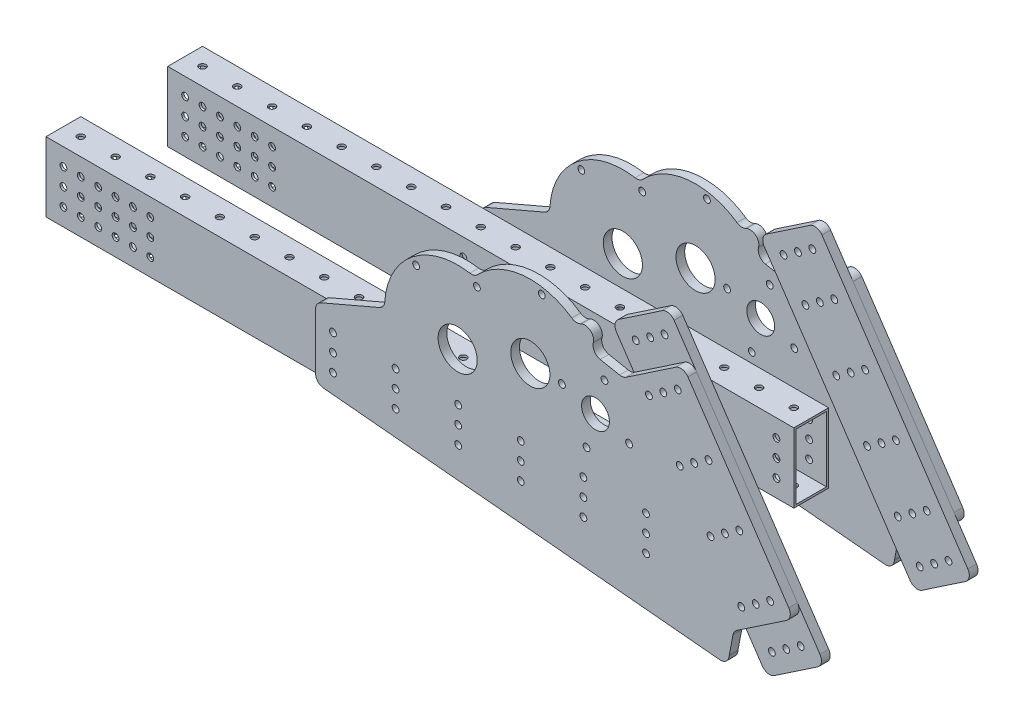
SolidWorks part; units mm, degrees
other "Markup1"
sketch "Sketch2"
sketch "Sketch9" plane through (0, 0, 0) normal (0, 0, 1) x (1, 0, 0)
sketch "Sketch12" plane through (116.0373, 167.646, 63.5) normal (0, 0, 1) x (1, 0, 0)
material "6061-T6 (SS)"
ref_plane "Front Plane" through (0, 0, 0) normal (0, 0, 1) x (1, 0, 0)
ref_plane "Top Plane" through (0, 0, 0) normal (0, 1, 0) x (1, 0, 0)
ref_plane "Right Plane" through (0, 0, 0) normal (1, 0, 0) x (0, 0, -1)
sketch "Grid" plane through (0, 0, 0) normal (0, 0, 1) x (1, 0, 0)
  line L0 (-23.2766, 0) -> (153.3593, 0) construction
  line L1 (0, 0) -> (0, 151.4205) construction
  line L6 (-1009.65, 1168.4) -> (-1009.65, 0) construction
  line L15 (-361.95, 520.7) -> (-803.275, 520.7)
  line L16 (-361.95, 520.7) -> (-361.95, 0)
  line L17 (-361.95, 0) -> (-803.275, 0)
  line L18 (-803.275, 520.7) -> (-803.275, 0)
  line L19 (-803.275, 0) -> (-1244.6, 0)
  line L20 (-803.275, 0) -> (-803.275, 825.5)
  line L21 (-803.275, 825.5) -> (-1244.6, 825.5)
  line L22 (-1244.6, 0) -> (-1244.6, 825.5)
  line L23 (-1030.732, 0) -> (-988.568, 0)
  line L24 (-1030.732, 0) -> (-1030.732, 1168.4)
  line L25 (-1030.732, 1168.4) -> (-988.568, 1168.4)
  line L26 (-988.568, 0) -> (-988.568, 1168.4)
  line L27 (-598.932, 0) -> (-556.768, 0)
  line L28 (-598.932, 0) -> (-598.932, 863.6)
  line L29 (-598.932, 863.6) -> (-556.768, 863.6)
  line L30 (-556.768, 0) -> (-556.768, 863.6)
  line L31 (-577.85, 863.6) -> (-577.85, 0) construction
  line L32 (-361.95, 520.7) -> (-361.95, 596.9) construction
  line L33 (-803.275, 825.5) -> (-803.275, 901.7) construction
  line L34 (-370.0766, 0) -> (-263.7141, 304.8)
  line L35 (-263.7141, 304.8) -> (-157.3516, 0)
  line L36 (-157.3516, 0) -> (-370.0766, 0)
  circle A0 centre (-100.3958, 159.9664) radius 120.65
  dimension "D3" = 241.3
  dimension "D2" = 76.2
  dimension "D4" = 304.8
  dimension "D5" = 212.725
  dimension "D7" = 42.164
  dimension "D8" = 520.7
  dimension "D9" = 304.8
  dimension "D10" = 1168.4
  dimension "D11" = 863.6
  dimension "D12" = 361.95
  dimension "D13" = 577.85
  dimension "D14" = 803.275
  dimension "D15" = 1009.65
sketch "ChassisXY" plane through (0, 0, 0) normal (0, 0, 1) x (1, 0, 0)
  line L0 (755.65, 93.726) -> (95.25, 93.726)
  line L1 (755.65, 93.726) -> (755.65, 42.926)
  line L2 (755.65, 42.926) -> (95.25, 42.926)
  line L3 (95.25, 93.726) -> (95.25, 42.926)
  line L15 (736.7108, 119.126) -> (675.4349, 119.126)
  line L16 (787.4, 42.926) -> (768.35, 42.926)
  line L19 (63.5, 169.926) -> (82.55, 169.926)
  line L20 (736.7108, 119.126) -> (694.5957, 90.719) construction
  line L21 (736.7108, 119.126) -> (717.55, 147.533) construction
  line L22 (694.5957, 90.719) -> (675.4349, 119.126) construction
  line L23 (717.55, 147.533) -> (675.4349, 119.126) construction
  line L27 (63.5, 169.926) -> (63.5, 42.926)
  line L31 (88.9, 42.926) -> (88.9, 1979.9925) construction
  line L32 (62.806, 1979.9925) -> (762, 1979.9925) construction
  line L33 (63.5, 42.926) -> (82.55, 42.926)
  line L36 (88.9, 1320.8) -> (762, 1320.8) construction
  line L37 (88.9, 988.6997) -> (131.0151, 1017.1067) construction
  line L45 (63.5, 42.926) -> (31.75, 42.926)
  line L46 (717.55, 147.533) -> (675.4349, 119.126) construction
  line L47 (717.55, 147.533) -> (-518.4596, 1979.9925) construction
  line L48 (675.4349, 119.126) -> (-560.5747, 1951.5855) construction
  line L49 (-518.4596, 1979.9925) -> (-560.5747, 1951.5855) construction
  line L50 (63.5, 42.926) -> (63.5, 169.926)
  line L51 (0, 74.676) -> (0, 138.176)
  line L52 (31.75, 169.926) -> (63.5, 169.926)
  line L54 (425.45, 93.726) -> (425.45, 42.926) construction
  line L55 (762, 42.926) -> (762, 1979.9925) construction
  line L56 (819.15, 169.926) -> (787.4, 169.926)
  line L57 (850.9, 74.676) -> (850.9, 138.176)
  line L58 (787.4, 42.926) -> (787.4, 169.926)
  line L59 (787.4, 42.926) -> (819.15, 42.926)
  line L60 (82.55, 169.926) -> (82.55, 42.926)
  line L61 (768.35, 169.926) -> (768.35, 42.926)
  line L62 (787.4, 169.926) -> (768.35, 169.926)
  line L63 (787.4, 169.926) -> (787.4, 42.926)
  line L64 (0, 0) -> (0, 200151.4205) construction
  line L65 (-200023.2766, 0) -> (200153.3593, 0) construction
  line L66 (95.25, 152.4) -> (755.65, 152.4) construction
  arc A5 (31.75, 169.926) -> (0, 138.176) centre (31.75, 138.176) ccw
  arc A6 (0, 74.676) -> (31.75, 42.926) centre (31.75, 74.676) ccw
  circle A7 centre (31.75, 74.676) radius 31.75 construction
  circle A8 centre (31.75, 138.176) radius 31.75 construction
  circle A9 centre (819.15, 138.176) radius 31.75 construction
  circle A10 centre (819.15, 74.676) radius 31.75 construction
  arc A11 (850.9, 74.676) -> (819.15, 42.926) centre (819.15, 74.676) cw
  arc A12 (819.15, 169.926) -> (850.9, 138.176) centre (819.15, 138.176) cw
  dimension "D3" = 63.5
  dimension "D1" = 50.8
  dimension "D2" = 56
  dimension "D4" = 38.1
  dimension "D5" = 50.8
  dimension "D6" = 12.7
  dimension "D7" = 19.05
  dimension "D8" = 42.926
  dimension "D9" = 109.474
  dimension "D10" = 25.4
  dimension "D12" = 660.4
  dimension "D13" = 6.35
ref_plane "Plane1" through (561.5696, 378.7835, 0) normal (0.829, 0.5592, 0) x (-0.5592, 0.829, 0)
sketch "carriage geo" plane through (0, 0, 0) normal (0, 0, 1) x (1, 0, 0)
  line L1 (116.0373, 195.326) -> (624.0373, 195.326)
  line L2 (116.0373, 195.326) -> (116.0373, 246.126)
  line L3 (116.0373, 246.126) -> (624.0373, 246.126)
  line L4 (624.0373, 195.326) -> (624.0373, 246.126)
  line L6 (624.0373, 195.326) -> (700.6322, 195.326) construction
  line L17 (717.55, 147.533) -> (-518.4596, 1979.9925) construction
  line L24 (624.0373, 246.126) -> (666.3671, 246.126) construction
  line L33 (666.3671, 246.126) -> (700.6322, 195.326) construction
  line L35 (675.4349, 119.126) -> (-560.5747, 1951.5855) construction
  line L64 (755.65, 93.726) -> (95.25, 93.726) construction
  circle A0 centre (154.1373, 220.726) radius 14.2875
  circle A58 centre (256.8816, 507.741) radius 25.4
  line B0 (120.4355, 364.2548) -> (144.4436, 355.656) construction
  line B1 (345.3934, 565.2279) -> (248.3868, 535.0242)
  line B2 (339.9907, 375.4447) -> (343.9447, 374.0285) construction
  line B3 (348.2442, 386.0326) -> (300.3235, 403.196) construction
  line B4 (308.577, 413.7839) -> (348.5895, 399.4529)
  line B5 (107.1432, 327.1426) -> (206.8255, 291.4401)
  line B6 (112.3162, 360.4178) -> (103.3062, 335.2619)
  line B7 (352.5436, 398.0367) -> (348.5895, 399.4529) construction
  line B8 (366.599, 439.1494) -> (341.413, 442.4393) construction
  line B9 (353.8882, 537.9448) -> (341.413, 442.4393) construction
  line B10 (343.9447, 374.0285) -> (352.5436, 398.0367)
  line B11 (348.5895, 399.4529) -> (308.577, 413.7839)
  line B12 (304.6229, 415.2001) -> (296.0241, 391.1919)
  line B13 (299.9781, 389.7757) -> (339.9907, 375.4447)
  line B14 (140.4752, 344.576) -> (141.8914, 348.5301) construction
  line B15 (129.3385, 325.9381) -> (133.2925, 324.5219) construction
  line B16 (110.7006, 337.0748) -> (109.2844, 333.1207) construction
  line B17 (121.8372, 355.7127) -> (117.8832, 357.1289) construction
  line B18 (117.8832, 357.1289) -> (110.7006, 337.0748)
  line B19 (109.2844, 333.1207) -> (129.3385, 325.9381)
  line B20 (141.8914, 348.5301) -> (121.8372, 355.7127)
  line B21 (133.2925, 324.5219) -> (140.4752, 344.576)
  line B22 (296.0241, 391.1919) -> (299.9781, 389.7757) construction
  line B23 (308.577, 413.7839) -> (304.6229, 415.2001) construction
  arc B24 (248.3868, 535.0242) -> (233.4586, 491.3735) centre (256.8816, 507.741) ccw
  circle B25 centre (256.8816, 507.741) radius 3.1877
  circle B26 centre (353.8882, 537.9448) radius 3.1877
  arc B27 (107.1432, 327.1426) -> (103.3062, 335.2619) centre (109.2844, 333.1207) cw
  circle B28 centre (341.413, 442.4393) radius 30 construction
  arc B29 (121.2422, 363.9009) -> (112.3162, 360.4178) centre (118.2943, 358.2767) ccw
  arc B30 (233.4586, 491.3735) -> (121.2422, 363.9009) centre (161.817, 441.3116) cw
  circle B31 centre (341.413, 442.4393) radius 25.4 construction
  circle B32 centre (366.599, 439.1494) radius 2.4892
  circle B33 centre (338.1231, 417.2533) radius 2.4892
  circle B34 centre (316.2269, 445.7292) radius 2.4892
  circle B35 centre (344.7029, 467.6254) radius 2.4892
  circle B36 centre (341.413, 442.4393) radius 10.16
  circle B37 centre (147.3899, 326.2177) radius 2.4892
  arc B38 (376.4624, 520.4251) -> (367.6342, 457.9958) centre (426.6271, 481.4924) ccw
  arc B39 (367.6342, 457.9958) -> (206.8255, 291.4401) centre (249.6484, 411.0026) cw
  arc B40 (133.2925, 324.5219) -> (129.3385, 325.9381) centre (131.3155, 325.23) cw
  arc B41 (343.9447, 374.0285) -> (339.9907, 375.4447) centre (341.9677, 374.7366) cw
  arc B42 (296.0241, 391.1919) -> (299.9781, 389.7757) centre (298.0011, 390.4838) ccw
  arc B43 (352.5436, 398.0367) -> (348.5895, 399.4529) centre (350.5666, 398.7448) ccw
  arc B44 (304.6229, 415.2001) -> (308.577, 413.7839) centre (306.5999, 414.492) cw
  arc B45 (109.2844, 333.1207) -> (110.7006, 337.0748) centre (109.9925, 335.0977) cw
  arc B46 (117.8832, 357.1289) -> (121.8372, 355.7127) centre (119.8602, 356.4208) cw
  arc B47 (141.8914, 348.5301) -> (140.4752, 344.576) centre (141.1833, 346.553) cw
  circle B48 centre (353.8882, 537.9448) radius 28.575
  line B49 (343.9447, 374.0285) -> (296.1197, 391.1577)
  line B50 (343.9447, 374.0285) -> (318.251, 302.291)
  line B51 (296.1197, 391.1577) -> (270.426, 319.4201)
  line B52 (318.251, 302.291) -> (270.426, 319.4201) construction
  line B53 (141.8571, 348.4344) -> (133.2925, 324.5219) construction
  line B54 (165.7696, 339.8698) -> (237.5071, 314.1761)
  line B55 (157.205, 315.9573) -> (228.9426, 290.2636)
  line B56 (237.5071, 314.1761) -> (228.9426, 290.2636) construction
  line B57 (161.4873, 327.9136) -> (233.2249, 302.2198) construction
  line B58 (165.7696, 339.8698) -> (157.205, 315.9573)
  line B59 (133.2925, 324.5219) -> (157.205, 315.9573) construction
  line B60 (141.8571, 348.4344) -> (165.7696, 339.8698) construction
  line B61 (308.4359, 312.5514) -> (331.9885, 378.3108) construction
  line B62 (320.0322, 382.5931) -> (294.3385, 310.8556) construction
  arc B63 (155.075, 274.6929) -> (165.7608, 168.0174) centre (154.1373, 220.726) ccw
  circle B64 centre (176.5553, 212.6967) radius 2.4892
  circle B65 centre (158.3928, 197.2968) radius 2.4892
  circle B66 centre (135.9748, 205.3261) radius 2.4892
  circle B67 centre (131.7194, 228.7553) radius 2.4892
  circle B68 centre (149.8819, 244.1552) radius 2.4892
  circle B69 centre (172.2999, 236.1259) radius 2.4892
  circle B70 centre (154.1373, 220.726) radius 23.8125 construction
  circle B71 centre (308.4359, 312.5514) radius 2.4892
  arc B72 (165.7608, 168.0174) -> (155.075, 274.6929) centre (154.1373, 220.726) ccw construction
  circle B73 centre (227.2467, 304.361) radius 2.4892
  circle B74 centre (284.5234, 321.116) radius 2.4892
  arc B75 (290.7123, 376.06) -> (193.2811, 330.0162) centre (218.9748, 401.7538) cw
  arc B76 (318.251, 302.291) -> (165.7608, 168.0174) centre (120.5341, 373.1059) cw
  circle B77 centre (312.7182, 324.5077) radius 2.4892
  circle B78 centre (288.8057, 333.0722) radius 2.4892
  circle B79 centre (317.0005, 336.4639) radius 2.4892
  circle B80 centre (293.088, 345.0285) radius 2.4892
  circle B81 centre (321.2828, 348.4202) radius 2.4892
  circle B82 centre (297.3703, 356.9847) radius 2.4892
  circle B83 centre (325.5651, 360.3764) radius 2.4892
  circle B84 centre (301.6526, 368.941) radius 2.4892
  circle B85 centre (329.8473, 372.3327) radius 2.4892
  circle B86 centre (305.9348, 380.8972) radius 2.4892
  arc B87 (162.2796, 314.1398) -> (155.075, 274.6929) centre (155.4279, 295.0098) cw
  circle B88 centre (215.2905, 308.6433) radius 2.4892
  circle B89 centre (203.3342, 312.9256) radius 2.4892
  circle B90 centre (191.378, 317.2079) radius 2.4892
  circle B91 centre (179.4217, 321.4901) radius 2.4892
  circle B92 centre (167.4655, 325.7724) radius 2.4892
  dimension "D2" = 28.575
  dimension "D3" = 25.4
  dimension "D4" = 38.1
  dimension "D8" = 101.6
  dimension "D5" = 50.8
  dimension "D1" = 50.8
  dimension "D6" = 12.7
  dimension "D7" = 508
sketch_block_instance "Block25-1"
sketch_block "Block25"
sketch_block_instance "Block26-1"
sketch_block "Block26"
sketch "carrriageyz" plane through (561.5696, 378.7835, 0) normal (0.829, 0.5592, 0) x (-0.5592, 0.829, 0)
  line L0 (-313.2035, 69.85) -> (769.957, 69.85) construction
  line L1 (769.957, -69.85) -> (-313.2035, -69.85) construction
  line L2 (-262.4035, 69.85) -> (-262.4035, -69.85) construction
  line L4 (-313.2035, 69.85) -> (-313.2035, -69.85) construction
  line L5 (-313.2035, 0) -> (-278.9385, 0) construction
  line L6 (769.957, 69.85) -> (769.957, -69.85) construction
  line L7 (-249.7114, 57.15) -> (-249.7114, 50.8)
  line L8 (-249.7114, 57.15) -> (-97.3114, 57.15)
  line L9 (-249.7114, 50.8) -> (-97.3114, 50.8)
  line L10 (-97.3114, 57.15) -> (-97.3114, 50.8)
  line L11 (1088.9959, 0) -> (-1088.9959, 0) construction
  line L12 (-97.3114, -57.15) -> (-97.3114, -50.8)
  line L13 (-249.7114, -50.8) -> (-97.3114, -50.8)
  line L14 (-249.7114, -57.15) -> (-97.3114, -57.15)
  line L15 (-249.7114, -57.15) -> (-249.7114, -50.8)
  line L16 (-218.5469, 31.75) -> (-148.6639, 31.75)
  line L17 (-174.4547, 57.15) -> (-206.8488, 57.15)
  line L19 (-221.2897, -57.15) -> (-160.0138, -57.15)
  line L21 (-219.5489, -57.15) -> (-127.4739, -57.15)
  line L22 (-219.5489, 63.5) -> (-127.4739, 63.5)
  line L23 (-219.5489, 63.5) -> (-219.5489, 57.15)
  line L24 (-219.5489, 57.15) -> (-127.4739, 57.15)
  line L25 (-127.4739, 63.5) -> (-127.4739, 57.15)
  line L26 (-127.4739, -63.5) -> (-127.4739, -57.15)
  line L27 (-219.5489, -63.5) -> (-127.4739, -63.5)
  line L28 (-219.5489, -63.5) -> (-219.5489, -57.15)
  line L29 (-218.5469, 31.75) -> (-218.5469, -31.75)
  line L30 (-218.5469, -31.75) -> (-148.6639, -31.75)
  line L31 (-148.6639, 31.75) -> (-148.6639, -31.75)
  line L33 (-97.3114, -69.1134) -> (-125.8864, -69.1134)
  line L34 (-97.3114, 57.15) -> (-125.8864, 57.15)
  line L35 (-97.3114, 57.15) -> (-97.3114, 69.1134)
  line L36 (-97.3114, 69.1134) -> (-125.8864, 69.1134)
  line L37 (-125.8864, 57.15) -> (-125.8864, 69.1134)
  line L38 (-249.7114, 57.15) -> (-221.1364, 57.15)
  line L39 (-249.7114, 57.15) -> (-249.7114, 69.1134)
  line L40 (-249.7114, 69.1134) -> (-221.1364, 69.1134)
  line L41 (-221.1364, 57.15) -> (-221.1364, 69.1134)
  line L42 (-125.8864, -57.15) -> (-125.8864, -69.1134)
  line L43 (-97.3114, -57.15) -> (-125.8864, -57.15)
  line L44 (-97.3114, -57.15) -> (-97.3114, -69.1134)
  line L45 (-249.7114, -69.1134) -> (-221.1364, -69.1134)
  line L46 (-221.1364, -57.15) -> (-221.1364, -69.1134)
  line L47 (-249.7114, -57.15) -> (-221.1364, -57.15)
  line L48 (-249.7114, -57.15) -> (-249.7114, -69.1134)
  line L49 (-111.5989, 69.1134) -> (-111.5989, -69.1134) construction
  line L50 (-235.4239, 69.1134) -> (-235.4239, -69.1134) construction
  point P4 (-313.2035, 0)
  point P31 (-148.6639, 0)
  point P41 (-190.6518, 57.15)
  point P53 (-111.5989, 0)
  dimension "D1" = 139.7
  dimension "D2" = 12.7
  dimension "D3" = 6.35
  dimension "D4" = 63.5
  dimension "D5" = 6.35
  dimension "D6" = 152.4
  dimension "D7" = 28.575
  dimension "D8" = 11.9634
  dimension "D9" = 50.8
  dimension "D10" = 1.5875
  dimension "D11" = 1.5875
ref_plane "bearing block interface plane" through (0, 0, 57.15) normal (0, 0, 1) x (1, 0, 0)
sketch "bearing block interface plate" plane through (0, 0, 57.15) normal (0, 0, 1) x (1, 0, 0)
  line L0 (529.0514, 336.1484) -> (571.1665, 364.5554)
  line L1 (529.0514, 336.1484) -> (642.6794, 167.688)
  line L2 (571.1665, 364.5554) -> (684.7945, 196.095)
  line L3 (642.6794, 167.688) -> (684.7945, 196.095)
  line L4 (675.4349, 119.126) -> (-560.5747, 1951.5855) construction
  line L5 (717.55, 147.533) -> (-518.4596, 1979.9925) construction
  line L6 (635.5777, 178.2167) -> (677.6928, 206.6237) construction
  line L7 (585.8654, 251.9182) -> (627.9805, 280.3252) construction
  line L8 (626.7005, 191.3777) -> (668.8156, 219.7847) construction
  line L10 (545.0304, 312.4586) -> (587.1455, 340.8656) construction
  line L12 (528.3092, 320.3288) -> (546.682, 332.7214) construction
  line L15 (606.2073, 289.894) -> (628.6962, 256.5529) construction
  line L16 (522.4272, 322.7212) -> (526.7202, 333.2764) construction
  line L17 (529.0514, 336.1484) -> (536.1532, 325.6196) construction
  line L18 (527.0768, 314.0996) -> (540.247, 311.4938) construction
  line L19 (627.7485, 166.576) -> (639.1433, 166.6024) construction
  line L20 (621.4964, 174.1167) -> (624.014, 187.3041) construction
  circle A0 centre (646.1065, 185.3185) radius 2.4892
  circle A1 centre (656.6352, 192.4202) radius 2.4892
  circle A2 centre (667.164, 199.522) radius 2.4892
  circle A3 centre (567.7395, 346.9249) radius 2.4892
  circle A4 centre (557.2107, 339.8231) radius 2.4892
  circle A5 centre (546.682, 332.7214) radius 2.4892
  arc A7 (522.4272, 322.7212) -> (527.0768, 314.0996) centre (528.3092, 320.3288) ccw construction
  circle A12 centre (562.6609, 309.0316) radius 2.4892
  circle A13 centre (573.1897, 316.1334) radius 2.4892
  circle A14 centre (583.7185, 323.2351) radius 2.4892
  circle A15 centre (606.2073, 289.894) radius 2.4892
  circle A16 centre (595.6786, 282.7922) radius 2.4892
  circle A17 centre (585.1498, 275.6905) radius 2.4892
  circle A18 centre (628.6962, 256.5529) radius 2.4892
  circle A19 centre (618.1674, 249.4511) radius 2.4892
  circle A20 centre (607.6387, 242.3494) radius 2.4892
  circle A21 centre (651.1851, 223.2117) radius 2.4892
  circle A22 centre (640.6563, 216.11) radius 2.4892
  circle A23 centre (630.1275, 209.0082) radius 2.4892
  arc A24 (526.7202, 333.2764) -> (529.0514, 336.1484) centre (532.6023, 330.884) cw construction
  arc A25 (540.247, 311.4938) -> (545.0304, 312.4586) centre (541.4795, 317.723) ccw construction
  arc A26 (639.1433, 166.6024) -> (642.6794, 167.688) centre (639.1286, 172.9523) ccw construction
  arc A27 (627.7485, 166.576) -> (621.4964, 174.1167) centre (627.7337, 172.9259) cw construction
  arc A28 (624.014, 187.3041) -> (626.7005, 191.3777) centre (630.2514, 186.1133) cw construction
  point P28 (617.4518, 273.2234)
  dimension "D3" = 4.9784
  dimension "D8" = 12.7
  dimension "D10" = 2
  dimension "D13" = 6.35
  dimension "D1" = 12.7
  dimension "D2" = 12.7
  dimension "D4" = 12.7
  dimension "D5" = 28.575
  dimension "D6" = 203.2
  dimension "D7" = 4.7625
  dimension "D9" = 9.4615
  dimension "D11" = 4
  dimension "D12" = 12.7
extrude "Boss-Extrude1" add sketch "bearing block interface plate" against normal blind 6.35
fillet "Fillet2" radius 6.35 4 edges at (642.6794, 167.688, 53.975) (571.1665, 364.5554, 53.975) (529.0514, 336.1484, 53.975) (684.7945, 196.095, 53.975)
ref_plane "carriage support plane" through (0, 0, 63.5) normal (0, 0, 1) x (1, 0, 0)
sketch "plate+gb" plane through (0, 0, 63.5) normal (0, 0, 1) x (1, 0, 0)
  line L1 (717.55, 147.533) -> (-518.4596, 1979.9925) construction
  line L3 (116.0373, 195.326) -> (624.0373, 195.326) construction
  line L4 (319.2373, 195.326) -> (627.1295, 166.4772)
  line L7 (668.3717, 220.4428) -> (587.5893, 340.2076)
  line L8 (509.1308, 327.7242) -> (407.5328, 284.067) construction
  line L9 (528.9804, 336.2537) -> (509.1308, 327.7242)
  line L10 (116.0373, 246.126) -> (624.0373, 246.126) construction
  line L11 (319.2373, 246.126) -> (319.2373, 195.326)
  line L12 (624.0373, 195.326) -> (624.0373, 246.126) construction
  line L13 (587.5893, 340.2076) -> (545.9795, 312.1414)
  line L16 (626.7619, 192.3766) -> (668.3717, 220.4428)
  line L17 (626.7005, 191.3777) -> (668.8156, 219.7847) construction
  line L18 (545.0304, 312.4586) -> (587.1455, 340.8656) construction
  line L19 (423.0019, 268.351) -> (154.1373, 220.726) construction
  line L20 (422.4031, 284.6145) -> (152.1515, 274.6645) construction
  line L21 (428.0259, 252.8714) -> (170.7996, 169.3872) construction
  line L22 (523.6581, 277.876) -> (530.2321, 302.4105) construction
  line L24 (369.6648, 267.7949) -> (319.2373, 246.126)
  line L26 (407.5328, 284.067) -> (369.6648, 267.7949) construction
  line L27 (435.2885, 320.2566) -> (440.2811, 305.1347) construction
  line L28 (623.8893, 187.3279) -> (621.3716, 174.1405)
  line L29 (627.7488, 166.449) -> (639.1436, 166.4754)
  line L30 (526.6026, 333.3242) -> (522.3095, 322.7691)
  line L31 (527.0521, 313.975) -> (540.2224, 311.3692)
  line L32 (526.6026, 333.3242) -> (522.3095, 322.7691)
  line L33 (527.0521, 313.975) -> (541.1961, 311.1765)
  line L34 (624.0754, 188.303) -> (621.3716, 174.1405)
  line L36 (389.6951, 310.0141) -> (397.6253, 300.0943) construction
  line L37 (485.2505, 338.4129) -> (483.0634, 325.9027) construction
  circle A0 centre (476.0648, 285.8698) radius 14.2875
  circle A1 centre (423.0019, 268.351) radius 14.2875
  arc A2 (155.075, 274.6929) -> (165.7608, 168.0174) centre (154.1373, 220.726) ccw construction
  arc A4 (165.7608, 168.0174) -> (155.075, 274.6929) centre (154.1373, 220.726) ccw construction
  circle A5 centre (523.6581, 277.876) radius 10.16
  circle A12 centre (523.6581, 277.876) radius 25.4 construction
  circle A13 centre (523.6581, 277.876) radius 7.62 construction
  circle A14 centre (476.0648, 285.8698) radius 40.64 construction
  circle A15 centre (476.0648, 285.8698) radius 15.24 construction
  circle A16 centre (423.0019, 268.351) radius 40.64 construction
  circle A17 centre (423.0019, 268.351) radius 16.2745 construction
  circle A18 centre (530.2321, 302.4105) radius 2.4892
  circle A19 centre (548.1926, 271.302) radius 2.4892
  circle A20 centre (517.0841, 253.3415) radius 2.4892
  circle A21 centre (499.1236, 284.45) radius 2.4892
  circle A22 centre (651.1851, 223.2117) radius 2.4892 construction
  circle A23 centre (640.6563, 216.11) radius 2.4892 construction
  circle A24 centre (630.1275, 209.0082) radius 2.4892 construction
  circle A25 centre (607.6387, 242.3494) radius 2.4892 construction
  circle A26 centre (618.1674, 249.4511) radius 2.4892 construction
  circle A27 centre (628.6962, 256.5529) radius 2.4892 construction
  circle A28 centre (606.2073, 289.894) radius 2.4892 construction
  circle A29 centre (595.6786, 282.7922) radius 2.4892 construction
  circle A30 centre (585.1498, 275.6905) radius 2.4892 construction
  circle A31 centre (562.6609, 309.0316) radius 2.4892 construction
  circle A32 centre (573.1897, 316.1334) radius 2.4892 construction
  circle A33 centre (583.7185, 323.2351) radius 2.4892 construction
  circle A34 centre (651.1851, 223.2117) radius 2.4892
  circle A35 centre (523.6581, 277.876) radius 30 construction
  circle A37 centre (640.6563, 216.11) radius 2.4892
  circle A40 centre (630.1275, 209.0082) radius 2.4892
  circle A41 centre (607.6387, 242.3494) radius 2.4892
  circle A42 centre (618.1674, 249.4511) radius 2.4892
  circle A43 centre (628.6962, 256.5529) radius 2.4892
  circle A44 centre (606.2073, 289.894) radius 2.4892
  circle A45 centre (595.6786, 282.7922) radius 2.4892
  circle A46 centre (585.1498, 275.6905) radius 2.4892
  circle A47 centre (562.6609, 309.0316) radius 2.4892
  circle A48 centre (573.1897, 316.1334) radius 2.4892
  circle A49 centre (583.7185, 323.2351) radius 2.4892
  circle A53 centre (528.3092, 320.3288) radius 9.525 construction
  arc A56 (435.2885, 320.2566) -> (369.6648, 267.7949) centre (423.0019, 268.351) ccw
  arc A57 (541.1961, 311.1765) -> (545.9795, 312.1414) centre (542.4286, 317.4058) ccw
  arc A58 (624.0754, 188.303) -> (626.7619, 192.3766) centre (630.3128, 187.1122) cw
  arc A59 (513.4373, 329.5747) -> (522.0656, 322.0516) centre (515.9443, 323.7406) cw
  arc A60 (626.6295, 191.483) -> (623.8893, 187.3279) centre (630.2514, 186.1133) ccw
  arc A61 (528.9804, 336.2537) -> (526.6026, 333.3242) centre (532.6023, 330.884) ccw
  arc A62 (522.3095, 322.7691) -> (527.0521, 313.975) centre (528.3092, 320.3288) ccw
  arc A63 (540.2224, 311.3692) -> (545.1014, 312.3534) centre (541.4795, 317.723) ccw
  arc A64 (528.9804, 336.2537) -> (526.6026, 333.3242) centre (532.6023, 330.884) ccw
  arc A65 (522.3095, 322.7691) -> (527.0521, 313.975) centre (528.3092, 320.3288) ccw
  arc A66 (621.3716, 174.1405) -> (627.7488, 166.449) centre (627.7337, 172.9259) ccw
  arc A67 (639.1436, 166.4754) -> (642.7505, 167.5827) centre (639.1286, 172.9523) ccw
  arc A68 (626.6295, 191.483) -> (623.8893, 187.3279) centre (630.2514, 186.1133) ccw
  arc A69 (621.3716, 174.1405) -> (627.1295, 166.4772) centre (627.7337, 172.9259) ccw
  arc A70 (435.2885, 320.2566) -> (509.1308, 327.7242) centre (476.0648, 285.8698) cw
  circle A71 centre (437.0751, 314.8453) radius 2.4892
  circle A72 centre (484.4304, 333.7216) radius 2.4892
  circle A73 centre (392.6689, 306.2942) radius 2.4892
  arc A74 (392.6689, 306.2942) -> (437.0751, 314.8453) centre (423.0019, 268.351) cw construction
  arc A75 (437.0751, 314.8453) -> (484.4304, 333.7216) centre (476.0648, 285.8698) cw construction
  circle A76 centre (392.6689, 306.2942) radius 4.7625 construction
  point P64 (523.6581, 277.876)
  point P133 (392.7822, 306.1525)
  dimension "D2" = 50.8
  dimension "D15" = 28.575
  dimension "D16" = 20.32
  dimension "D18" = 4.9784
  dimension "D14" = 6.35
  dimension "D23" = 19.05
  dimension "D25" = 4.9784
  dimension "D27" = 9.525
  dimension "D1" = 304.8
  dimension "D11" = 0.7937
  dimension "D12" = 0.7937
  dimension "D19" = 15
  dimension "D8" = 273.05
  dimension "D10" = 22.225
  dimension "D9" = 25.4
  dimension "D20" = 31.75
  dimension "D24" = 12.7
  dimension "D26" = 50.8
  dimension "D13" = 0.127
  dimension "D21" = 0.127
  dimension "D17" = 4
extrude "Boss-Extrude2" add sketch "plate+gb" against normal blind 6.35 separate body contours A69 L34 A58 L16 L7 L13 A57 L33 A65 L32 A64 L9 L11 L4 A49 A48 A47 A46 A45 A44 A43 A42 A41 A40 A37 A34 A21 A20 A19 A18 A5 A1 region at (496.568, 246.5045, 63.5)
fillet "Fillet1" radius 6.35 8 edges at (668.3717, 220.4428, 60.325) (587.5893, 340.2076, 60.325) (319.2373, 195.326, 60.325) (627.1295, 166.4772, 60.325) (435.2885, 320.2566, 60.325) (369.6648, 267.7949, 60.325) (509.1308, 327.7242, 60.325) (319.2373, 246.126, 60.325)
ref_plane "tubeplate" through (0, 0, 57.15) normal (0, 0, 1) x (1, 0, 0)
sketch "tube" plane through (0, 0, 57.15) normal (0, 0, 1) x (1, 0, 0)
  line L0 (116.0373, 246.126) -> (624.0373, 246.126) construction
  line L1 (573.2373, 246.126) -> (116.0373, 246.126)
  line L2 (573.2373, 246.126) -> (573.2373, 195.326)
  line L3 (573.2373, 195.326) -> (116.0373, 195.326)
  line L4 (116.0373, 246.126) -> (116.0373, 195.326)
  line L6 (624.0373, 195.326) -> (624.0373, 246.126) construction
  line L7 (560.5373, 246.126) -> (560.5373, 195.326) construction
  line L8 (319.2373, 246.126) -> (319.2373, 195.326) construction
  line L9 (128.7373, 246.126) -> (128.7373, 195.326) construction
  line L10 (116.0373, 195.326) -> (624.0373, 195.326) construction
  circle A0 centre (560.5373, 220.726) radius 2.4892
  circle A1 centre (560.5373, 208.026) radius 2.4892
  circle A2 centre (560.5373, 233.426) radius 2.4892
  circle A3 centre (514.8173, 208.026) radius 2.4892
  circle A4 centre (514.8173, 220.726) radius 2.4892
  circle A5 centre (514.8173, 233.426) radius 2.4892
  circle A6 centre (469.0973, 208.026) radius 2.4892
  circle A7 centre (469.0973, 220.726) radius 2.4892
  circle A8 centre (469.0973, 233.426) radius 2.4892
  circle A9 centre (423.3773, 208.026) radius 2.4892
  circle A10 centre (423.3773, 220.726) radius 2.4892
  circle A11 centre (423.3773, 233.426) radius 2.4892
  circle A12 centre (377.6573, 208.026) radius 2.4892
  circle A13 centre (377.6573, 220.726) radius 2.4892
  circle A14 centre (377.6573, 233.426) radius 2.4892
  circle A15 centre (331.9373, 208.026) radius 2.4892
  circle A16 centre (331.9373, 220.726) radius 2.4892
  circle A17 centre (331.9373, 233.426) radius 2.4892
  circle A18 centre (128.7373, 220.726) radius 2.4892
  circle A19 centre (128.7373, 208.026) radius 2.4892
  circle A20 centre (128.7373, 233.426) radius 2.4892
  circle A21 centre (141.4373, 220.726) radius 2.4892
  circle A22 centre (141.4373, 208.026) radius 2.4892
  circle A23 centre (141.4373, 233.426) radius 2.4892
  circle A24 centre (154.1373, 220.726) radius 2.4892
  circle A25 centre (154.1373, 208.026) radius 2.4892
  circle A26 centre (154.1373, 233.426) radius 2.4892
  circle A27 centre (166.8373, 220.726) radius 2.4892
  circle A28 centre (166.8373, 208.026) radius 2.4892
  circle A29 centre (166.8373, 233.426) radius 2.4892
  circle A30 centre (179.5373, 220.726) radius 2.4892
  circle A31 centre (179.5373, 208.026) radius 2.4892
  circle A32 centre (179.5373, 233.426) radius 2.4892
  circle A33 centre (192.2373, 220.726) radius 2.4892
  circle A34 centre (192.2373, 208.026) radius 2.4892
  circle A35 centre (192.2373, 233.426) radius 2.4892
  dimension "D3" = 4.9784
  dimension "D8" = 4.9784
  dimension "D1" = 50.8
  dimension "D2" = 12.7
  dimension "D4" = 12.7
  dimension "D5" = 12.7
  dimension "D7" = 12.7
  dimension "D9" = 12.7
  dimension "D10" = 12.7
  dimension "D11" = 12.7
  dimension "D13" = 12.7
  dimension "D6" = 6
  dimension "D12" = 6
extrude "Boss-Extrude3" add sketch "tube" against normal blind 25.4 separate body contours L1 L4 L3 L2 A35 A34 A33 A32 A31 A30 A29 A28 A27 A26 A25 A24 A23 A22 A21 A20 A19 A18 A17 A16 A15 A14 A13 | A2 | A0 | A1 | A3 | A4 | A5 | A8 | A7 | A9 | A6 | A10 | A17 | A14 | A13 | A12 | A15 | A16 | A11 | A35 | A32 | A29 | A26 | A23 | A20 | A18 | A21 | A24 | A27 | A30 | A33 | A34 | A31 | A28 | A25 | A22 | A19 region at (345.9214, 220.726, 57.15) region at (560.5373, 220.726, 57.15) region at (560.5373, 208.026, 57.15) region at (560.5373, 233.426, 57.15) region at (514.8173, 208.026, 57.15) region at (514.8173, 220.726, 57.15) region at (514.8173, 233.426, 57.15) region at (469.0973, 208.026, 57.15) region at (469.0973, 220.726, 57.15) region at (469.0973, 233.426, 57.15) region at (423.3773, 208.026, 57.15) region at (423.3773, 220.726, 57.15) region at (423.3773, 233.426, 57.15) region at (377.6573, 208.026, 57.15) region at (377.6573, 220.726, 57.15) region at (377.6573, 233.426, 57.15) region at (331.9373, 208.026, 57.15) region at (331.9373, 220.726, 57.15) region at (331.9373, 233.426, 57.15) region at (128.7373, 220.726, 57.15) region at (128.7373, 208.026, 57.15) region at (128.7373, 233.426, 57.15) region at (141.4373, 220.726, 57.15) region at (141.4373, 208.026, 57.15) region at (141.4373, 233.426, 57.15) region at (154.1373, 220.726, 57.15) region at (154.1373, 208.026, 57.15) region at (154.1373, 233.426, 57.15) region at (166.8373, 220.726, 57.15) region at (166.8373, 208.026, 57.15) region at (166.8373, 233.426, 57.15) region at (179.5373, 220.726, 57.15) region at (179.5373, 208.026, 57.15) region at (179.5373, 233.426, 57.15) region at (192.2373, 220.726, 57.15) region at (192.2373, 208.026, 57.15) region at (192.2373, 233.426, 57.15)
shell "Shell2" thickness 1.5875 removed face at (573.2373, 220.726, 44.45) removed face at (116.0373, 220.726, 44.45)
sketch "Sketch11" plane through (0, 246.126, 0) normal (0, 1, 0) x (1, 0, 0)
  line L0 (116.0373, -44.45) -> (573.2373, -44.45) construction
  line L1 (116.0373, -31.75) -> (116.0373, -57.15) construction
  line L2 (573.2373, -31.75) -> (573.2373, -57.15) construction
  circle A0 centre (560.5373, -44.45) radius 2.4892
  circle A1 centre (535.1373, -44.45) radius 2.4892
  circle A2 centre (509.7373, -44.45) radius 2.4892
  circle A3 centre (484.3373, -44.45) radius 2.4892
  circle A4 centre (458.9373, -44.45) radius 2.4892
  circle A5 centre (433.5373, -44.45) radius 2.4892
  circle A6 centre (408.1373, -44.45) radius 2.4892
  circle A7 centre (382.7373, -44.45) radius 2.4892
  circle A8 centre (357.3373, -44.45) radius 2.4892
  circle A9 centre (331.9373, -44.45) radius 2.4892
  circle A10 centre (306.5373, -44.45) radius 2.4892
  circle A11 centre (281.1373, -44.45) radius 2.4892
  circle A12 centre (255.7373, -44.45) radius 2.4892
  circle A13 centre (230.3373, -44.45) radius 2.4892
  circle A14 centre (204.9373, -44.45) radius 2.4892
  circle A15 centre (179.5373, -44.45) radius 2.4892
  circle A16 centre (154.1373, -44.45) radius 2.4892
  circle A17 centre (128.7373, -44.45) radius 2.4892
  dimension "D1" = 4.9784
  dimension "D2" = 12.7
  dimension "D4" = 25.4
  dimension "D3" = 18
extrude "Cut-Extrude4" cut sketch "Sketch11" against normal through all
extrude "Cut-Extrude2" cut sketch "tube<4>" against normal through all contours A2 | A0 | A1 | A3 | A4 | A5 | A8 | A7 | A10 | A11 | A14 | A12 | A17 | A16 | A35 | A34 | A32 | A30 | A29 | A27 | A24 | A22 | A19 | A31 | A6 | A9 | A13 | A15 | A33 | A26 | A23 | A20 | A18 | A21 | A25 | A28 region at (560.5373, 220.726, 57.15) region at (560.5373, 208.026, 57.15) region at (560.5373, 233.426, 57.15) region at (514.8173, 208.026, 57.15) region at (514.8173, 220.726, 57.15) region at (514.8173, 233.426, 57.15) region at (469.0973, 220.726, 57.15) region at (469.0973, 233.426, 57.15) region at (423.3773, 220.726, 57.15) region at (423.3773, 233.426, 57.15) region at (377.6573, 208.026, 57.15) region at (377.6573, 233.426, 57.15) region at (331.9373, 220.726, 57.15) region at (331.9373, 233.426, 57.15) region at (128.7373, 208.026, 57.15) region at (141.4373, 208.026, 57.15) region at (154.1373, 220.726, 57.15) region at (166.8373, 220.726, 57.15) region at (166.8373, 233.426, 57.15) region at (179.5373, 220.726, 57.15) region at (179.5373, 208.026, 57.15) region at (179.5373, 233.426, 57.15) region at (192.2373, 208.026, 57.15) region at (192.2373, 233.426, 57.15)
sketch "tube<4>" plane through (0, 0, 57.15) normal (0, 0, 1) x (1, 0, 0) same geometry as "tube"
sketch "Sketch10" plane through (0, 0, 63.5) normal (0, 0, 1) x (1, 0, 0)
  circle A0 centre (469.0973, 208.026) radius 2.4892 construction
  circle A1 centre (423.3773, 208.026) radius 2.4892 construction
  circle A2 centre (377.6573, 208.026) radius 2.4892 construction
  circle A3 centre (331.9373, 208.026) radius 2.4892 construction
  circle A4 centre (331.9373, 220.726) radius 2.4892 construction
  circle A5 centre (377.6573, 220.726) radius 2.4892 construction
  circle A6 centre (423.3773, 220.726) radius 2.4892 construction
  circle A7 centre (469.0973, 220.726) radius 2.4892 construction
  circle A8 centre (514.8173, 220.726) radius 2.4892 construction
  circle A9 centre (514.8173, 208.026) radius 2.4892 construction
  circle A10 centre (560.5373, 208.026) radius 2.4892 construction
  circle A11 centre (560.5373, 220.726) radius 2.4892 construction
  circle A12 centre (560.5373, 233.426) radius 2.4892 construction
  circle A13 centre (514.8173, 233.426) radius 2.4892 construction
  circle A14 centre (469.0973, 233.426) radius 2.4892 construction
  circle A15 centre (423.3773, 233.426) radius 2.4892 construction
  circle A16 centre (377.6573, 233.426) radius 2.4892 construction
  circle A17 centre (331.9373, 233.426) radius 2.4892 construction
  circle A18 centre (469.0973, 208.026) radius 2.4892
  circle A19 centre (423.3773, 208.026) radius 2.4892
  circle A20 centre (377.6573, 208.026) radius 2.4892
  circle A21 centre (331.9373, 208.026) radius 2.4892
  circle A22 centre (331.9373, 220.726) radius 2.4892
  circle A23 centre (377.6573, 220.726) radius 2.4892
  circle A24 centre (423.3773, 220.726) radius 2.4892
  circle A25 centre (469.0973, 220.726) radius 2.4892
  circle A26 centre (514.8173, 220.726) radius 2.4892
  circle A27 centre (514.8173, 208.026) radius 2.4892
  circle A28 centre (560.5373, 208.026) radius 2.4892
  circle A29 centre (560.5373, 220.726) radius 2.4892
  circle A30 centre (560.5373, 233.426) radius 2.4892
  circle A31 centre (514.8173, 233.426) radius 2.4892
  circle A32 centre (469.0973, 233.426) radius 2.4892
  circle A33 centre (423.3773, 233.426) radius 2.4892
  circle A34 centre (377.6573, 233.426) radius 2.4892
  circle A35 centre (331.9373, 233.426) radius 2.4892
extrude "Cut-Extrude3" cut sketch "Sketch10" against normal through all
mirror "Mirror1" about plane through (0, 0, 0) normal (0, 0, 1) of bodies 105 104 101
equation "\"D3@plate+gb\" = 12 / 20"
equation "\"D4@plate+gb\" = 64 / 20"
equation "\"D5@plate+gb\" = 24 / 20"
equation "\"D6@plate+gb\" = 64 / 20"
equation "\"D7@plate+gb\" = 0.25 /  ( sin ( 180 / 16 )  ) "
equation "\"D22@plate+gb\"=60mm"
